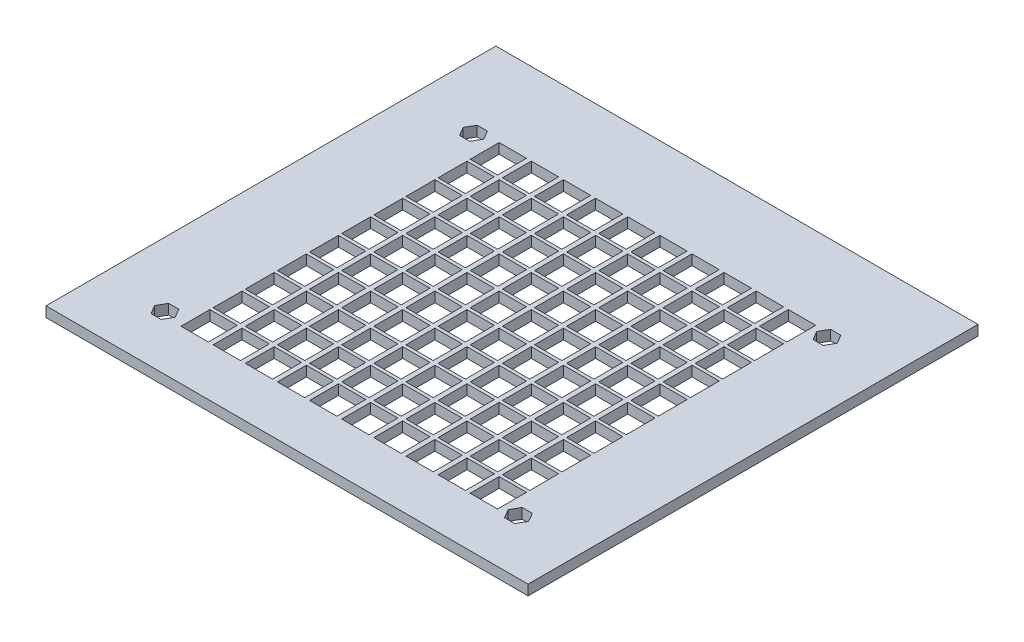
SolidWorks part; units mm, degrees
ref_plane "Front Plane" through (0, 0, 0) normal (0, 0, 1) x (1, 0, 0)
ref_plane "Top Plane" through (0, 0, 0) normal (0, 1, 0) x (1, 0, 0)
ref_plane "Right Plane" through (0, 0, 0) normal (1, 0, 0) x (0, 0, -1)
sketch "Sketch1" plane through (0, 0, 0) normal (0, 1, 0) x (1, 0, 0)
  line L0 (130, 101) -> (20, 101) construction
  line L2 (0, 0) -> (0, 106)
  line L4 (150, 0) -> (150, 106)
  line L6 (130, 101) -> (130, 5) construction
  line L8 (21.5877, 98.25) -> (23.1754, 101)
  line L9 (23.1754, 101) -> (21.5877, 103.75)
  line L10 (21.5877, 103.75) -> (18.4123, 103.75)
  line L11 (18.4123, 103.75) -> (16.8246, 101)
  line L12 (16.8246, 101) -> (18.4123, 98.25)
  line L13 (18.4123, 98.25) -> (21.5877, 98.25)
  line L14 (36.5, 12.5) -> (36.5, 3.5)
  line L15 (26.5, 12.5) -> (35, 12.5)
  line L16 (26.5, 12.5) -> (26.5, 3.5)
  line L17 (26.5, 3.5) -> (35, 3.5)
  line L18 (35, 12.5) -> (35, 3.5)
  line L19 (36.5, 12.5) -> (45, 12.5)
  line L20 (45, 12.5) -> (45, 3.5)
  line L21 (36.5, 3.5) -> (45, 3.5)
  line L22 (46.5, 12.5) -> (46.5, 3.5)
  line L23 (46.5, 12.5) -> (55, 12.5)
  line L24 (55, 12.5) -> (55, 3.5)
  line L25 (46.5, 3.5) -> (55, 3.5)
  line L26 (56.5, 12.5) -> (56.5, 3.5)
  line L27 (56.5, 12.5) -> (65, 12.5)
  line L28 (65, 12.5) -> (65, 3.5)
  line L29 (56.5, 3.5) -> (65, 3.5)
  line L30 (66.5, 12.5) -> (66.5, 3.5)
  line L31 (66.5, 12.5) -> (75, 12.5)
  line L32 (75, 12.5) -> (75, 3.5)
  line L33 (66.5, 3.5) -> (75, 3.5)
  line L34 (76.5, 12.5) -> (76.5, 3.5)
  line L35 (76.5, 12.5) -> (85, 12.5)
  line L36 (85, 12.5) -> (85, 3.5)
  line L37 (76.5, 3.5) -> (85, 3.5)
  line L38 (86.5, 12.5) -> (86.5, 3.5)
  line L39 (86.5, 12.5) -> (95, 12.5)
  line L40 (95, 12.5) -> (95, 3.5)
  line L41 (86.5, 3.5) -> (95, 3.5)
  line L42 (96.5, 12.5) -> (96.5, 3.5)
  line L43 (96.5, 12.5) -> (105, 12.5)
  line L44 (105, 12.5) -> (105, 3.5)
  line L45 (96.5, 3.5) -> (105, 3.5)
  line L46 (106.5, 12.5) -> (106.5, 3.5)
  line L47 (106.5, 12.5) -> (115, 12.5)
  line L48 (115, 12.5) -> (115, 3.5)
  line L49 (106.5, 3.5) -> (115, 3.5)
  line L50 (116.5, 12.5) -> (116.5, 3.5)
  line L51 (116.5, 12.5) -> (125, 12.5)
  line L52 (125, 12.5) -> (125, 3.5)
  line L53 (116.5, 3.5) -> (125, 3.5)
  line L54 (36.5, 22.5) -> (36.5, 13.5)
  line L55 (36.5, 22.5) -> (45, 22.5)
  line L56 (45, 22.5) -> (45, 13.5)
  line L57 (36.5, 13.5) -> (45, 13.5)
  line L58 (46.5, 22.5) -> (46.5, 13.5)
  line L59 (46.5, 22.5) -> (55, 22.5)
  line L60 (55, 22.5) -> (55, 13.5)
  line L61 (46.5, 13.5) -> (55, 13.5)
  line L62 (56.5, 22.5) -> (56.5, 13.5)
  line L63 (56.5, 22.5) -> (65, 22.5)
  line L64 (65, 22.5) -> (65, 13.5)
  line L65 (56.5, 13.5) -> (65, 13.5)
  line L66 (66.5, 22.5) -> (66.5, 13.5)
  line L67 (66.5, 22.5) -> (75, 22.5)
  line L68 (75, 22.5) -> (75, 13.5)
  line L69 (66.5, 13.5) -> (75, 13.5)
  line L70 (76.5, 22.5) -> (76.5, 13.5)
  line L71 (76.5, 22.5) -> (85, 22.5)
  line L72 (85, 22.5) -> (85, 13.5)
  line L73 (76.5, 13.5) -> (85, 13.5)
  line L74 (86.5, 22.5) -> (86.5, 13.5)
  line L75 (86.5, 22.5) -> (95, 22.5)
  line L76 (95, 22.5) -> (95, 13.5)
  line L77 (86.5, 13.5) -> (95, 13.5)
  line L78 (96.5, 22.5) -> (96.5, 13.5)
  line L79 (96.5, 22.5) -> (105, 22.5)
  line L80 (105, 22.5) -> (105, 13.5)
  line L81 (96.5, 13.5) -> (105, 13.5)
  line L82 (106.5, 22.5) -> (106.5, 13.5)
  line L83 (106.5, 22.5) -> (115, 22.5)
  line L84 (115, 22.5) -> (115, 13.5)
  line L85 (106.5, 13.5) -> (115, 13.5)
  line L86 (116.5, 22.5) -> (116.5, 13.5)
  line L87 (116.5, 22.5) -> (125, 22.5)
  line L88 (125, 22.5) -> (125, 13.5)
  line L89 (116.5, 13.5) -> (125, 13.5)
  line L90 (36.5, 32.5) -> (36.5, 23.5)
  line L91 (36.5, 32.5) -> (45, 32.5)
  line L92 (45, 32.5) -> (45, 23.5)
  line L93 (36.5, 23.5) -> (45, 23.5)
  line L94 (46.5, 32.5) -> (46.5, 23.5)
  line L95 (46.5, 32.5) -> (55, 32.5)
  line L96 (55, 32.5) -> (55, 23.5)
  line L97 (46.5, 23.5) -> (55, 23.5)
  line L98 (56.5, 32.5) -> (56.5, 23.5)
  line L99 (56.5, 32.5) -> (65, 32.5)
  line L100 (65, 32.5) -> (65, 23.5)
  line L101 (56.5, 23.5) -> (65, 23.5)
  line L102 (66.5, 32.5) -> (66.5, 23.5)
  line L103 (66.5, 32.5) -> (75, 32.5)
  line L104 (75, 32.5) -> (75, 23.5)
  line L105 (66.5, 23.5) -> (75, 23.5)
  line L106 (76.5, 32.5) -> (76.5, 23.5)
  line L107 (76.5, 32.5) -> (85, 32.5)
  line L108 (85, 32.5) -> (85, 23.5)
  line L109 (76.5, 23.5) -> (85, 23.5)
  line L110 (86.5, 32.5) -> (86.5, 23.5)
  line L111 (86.5, 32.5) -> (95, 32.5)
  line L112 (95, 32.5) -> (95, 23.5)
  line L113 (86.5, 23.5) -> (95, 23.5)
  line L114 (96.5, 32.5) -> (96.5, 23.5)
  line L115 (96.5, 32.5) -> (105, 32.5)
  line L116 (105, 32.5) -> (105, 23.5)
  line L117 (96.5, 23.5) -> (105, 23.5)
  line L118 (106.5, 32.5) -> (106.5, 23.5)
  line L119 (106.5, 32.5) -> (115, 32.5)
  line L120 (115, 32.5) -> (115, 23.5)
  line L121 (106.5, 23.5) -> (115, 23.5)
  line L122 (116.5, 32.5) -> (116.5, 23.5)
  line L123 (116.5, 32.5) -> (125, 32.5)
  line L124 (125, 32.5) -> (125, 23.5)
  line L125 (116.5, 23.5) -> (125, 23.5)
  line L126 (36.5, 42.5) -> (36.5, 33.5)
  line L127 (36.5, 42.5) -> (45, 42.5)
  line L128 (45, 42.5) -> (45, 33.5)
  line L129 (36.5, 33.5) -> (45, 33.5)
  line L130 (46.5, 42.5) -> (46.5, 33.5)
  line L131 (46.5, 42.5) -> (55, 42.5)
  line L132 (55, 42.5) -> (55, 33.5)
  line L133 (46.5, 33.5) -> (55, 33.5)
  line L134 (56.5, 42.5) -> (56.5, 33.5)
  line L135 (56.5, 42.5) -> (65, 42.5)
  line L136 (65, 42.5) -> (65, 33.5)
  line L137 (56.5, 33.5) -> (65, 33.5)
  line L138 (66.5, 42.5) -> (66.5, 33.5)
  line L139 (66.5, 42.5) -> (75, 42.5)
  line L140 (75, 42.5) -> (75, 33.5)
  line L141 (66.5, 33.5) -> (75, 33.5)
  line L142 (76.5, 42.5) -> (76.5, 33.5)
  line L143 (76.5, 42.5) -> (85, 42.5)
  line L144 (85, 42.5) -> (85, 33.5)
  line L145 (76.5, 33.5) -> (85, 33.5)
  line L146 (86.5, 42.5) -> (86.5, 33.5)
  line L147 (86.5, 42.5) -> (95, 42.5)
  line L148 (95, 42.5) -> (95, 33.5)
  line L149 (86.5, 33.5) -> (95, 33.5)
  line L150 (96.5, 42.5) -> (96.5, 33.5)
  line L151 (96.5, 42.5) -> (105, 42.5)
  line L152 (105, 42.5) -> (105, 33.5)
  line L153 (96.5, 33.5) -> (105, 33.5)
  line L154 (106.5, 42.5) -> (106.5, 33.5)
  line L155 (106.5, 42.5) -> (115, 42.5)
  line L156 (115, 42.5) -> (115, 33.5)
  line L157 (106.5, 33.5) -> (115, 33.5)
  line L158 (116.5, 42.5) -> (116.5, 33.5)
  line L159 (116.5, 42.5) -> (125, 42.5)
  line L160 (125, 42.5) -> (125, 33.5)
  line L161 (116.5, 33.5) -> (125, 33.5)
  line L162 (36.5, 52.5) -> (36.5, 43.5)
  line L163 (36.5, 52.5) -> (45, 52.5)
  line L164 (45, 52.5) -> (45, 43.5)
  line L165 (36.5, 43.5) -> (45, 43.5)
  line L166 (46.5, 52.5) -> (46.5, 43.5)
  line L167 (46.5, 52.5) -> (55, 52.5)
  line L168 (55, 52.5) -> (55, 43.5)
  line L169 (46.5, 43.5) -> (55, 43.5)
  line L170 (56.5, 52.5) -> (56.5, 43.5)
  line L171 (56.5, 52.5) -> (65, 52.5)
  line L172 (65, 52.5) -> (65, 43.5)
  line L173 (56.5, 43.5) -> (65, 43.5)
  line L174 (66.5, 52.5) -> (66.5, 43.5)
  line L175 (66.5, 52.5) -> (75, 52.5)
  line L176 (75, 52.5) -> (75, 43.5)
  line L177 (66.5, 43.5) -> (75, 43.5)
  line L178 (76.5, 52.5) -> (76.5, 43.5)
  line L179 (76.5, 52.5) -> (85, 52.5)
  line L180 (85, 52.5) -> (85, 43.5)
  line L181 (76.5, 43.5) -> (85, 43.5)
  line L182 (86.5, 52.5) -> (86.5, 43.5)
  line L183 (86.5, 52.5) -> (95, 52.5)
  line L184 (95, 52.5) -> (95, 43.5)
  line L185 (86.5, 43.5) -> (95, 43.5)
  line L186 (96.5, 52.5) -> (96.5, 43.5)
  line L187 (96.5, 52.5) -> (105, 52.5)
  line L188 (105, 52.5) -> (105, 43.5)
  line L189 (96.5, 43.5) -> (105, 43.5)
  line L190 (106.5, 52.5) -> (106.5, 43.5)
  line L191 (106.5, 52.5) -> (115, 52.5)
  line L192 (115, 52.5) -> (115, 43.5)
  line L193 (106.5, 43.5) -> (115, 43.5)
  line L194 (116.5, 52.5) -> (116.5, 43.5)
  line L195 (116.5, 52.5) -> (125, 52.5)
  line L196 (125, 52.5) -> (125, 43.5)
  line L197 (116.5, 43.5) -> (125, 43.5)
  line L198 (36.5, 62.5) -> (36.5, 53.5)
  line L199 (36.5, 62.5) -> (45, 62.5)
  line L200 (45, 62.5) -> (45, 53.5)
  line L201 (36.5, 53.5) -> (45, 53.5)
  line L202 (46.5, 62.5) -> (46.5, 53.5)
  line L203 (46.5, 62.5) -> (55, 62.5)
  line L204 (55, 62.5) -> (55, 53.5)
  line L205 (46.5, 53.5) -> (55, 53.5)
  line L206 (56.5, 62.5) -> (56.5, 53.5)
  line L207 (56.5, 62.5) -> (65, 62.5)
  line L208 (65, 62.5) -> (65, 53.5)
  line L209 (56.5, 53.5) -> (65, 53.5)
  line L210 (66.5, 62.5) -> (66.5, 53.5)
  line L211 (66.5, 62.5) -> (75, 62.5)
  line L212 (75, 62.5) -> (75, 53.5)
  line L213 (66.5, 53.5) -> (75, 53.5)
  line L214 (76.5, 62.5) -> (76.5, 53.5)
  line L215 (76.5, 62.5) -> (85, 62.5)
  line L216 (85, 62.5) -> (85, 53.5)
  line L217 (76.5, 53.5) -> (85, 53.5)
  line L218 (86.5, 62.5) -> (86.5, 53.5)
  line L219 (86.5, 62.5) -> (95, 62.5)
  line L220 (95, 62.5) -> (95, 53.5)
  line L221 (86.5, 53.5) -> (95, 53.5)
  line L222 (96.5, 62.5) -> (96.5, 53.5)
  line L223 (96.5, 62.5) -> (105, 62.5)
  line L224 (105, 62.5) -> (105, 53.5)
  line L225 (96.5, 53.5) -> (105, 53.5)
  line L226 (106.5, 62.5) -> (106.5, 53.5)
  line L227 (106.5, 62.5) -> (115, 62.5)
  line L228 (115, 62.5) -> (115, 53.5)
  line L229 (106.5, 53.5) -> (115, 53.5)
  line L230 (116.5, 62.5) -> (116.5, 53.5)
  line L231 (116.5, 62.5) -> (125, 62.5)
  line L232 (125, 62.5) -> (125, 53.5)
  line L233 (116.5, 53.5) -> (125, 53.5)
  line L234 (36.5, 72.5) -> (36.5, 63.5)
  line L235 (36.5, 72.5) -> (45, 72.5)
  line L236 (45, 72.5) -> (45, 63.5)
  line L237 (36.5, 63.5) -> (45, 63.5)
  line L238 (46.5, 72.5) -> (46.5, 63.5)
  line L239 (46.5, 72.5) -> (55, 72.5)
  line L240 (55, 72.5) -> (55, 63.5)
  line L241 (46.5, 63.5) -> (55, 63.5)
  line L242 (56.5, 72.5) -> (56.5, 63.5)
  line L243 (56.5, 72.5) -> (65, 72.5)
  line L244 (65, 72.5) -> (65, 63.5)
  line L245 (56.5, 63.5) -> (65, 63.5)
  line L246 (66.5, 72.5) -> (66.5, 63.5)
  line L247 (66.5, 72.5) -> (75, 72.5)
  line L248 (75, 72.5) -> (75, 63.5)
  line L249 (66.5, 63.5) -> (75, 63.5)
  line L250 (76.5, 72.5) -> (76.5, 63.5)
  line L251 (76.5, 72.5) -> (85, 72.5)
  line L252 (85, 72.5) -> (85, 63.5)
  line L253 (76.5, 63.5) -> (85, 63.5)
  line L254 (86.5, 72.5) -> (86.5, 63.5)
  line L255 (86.5, 72.5) -> (95, 72.5)
  line L256 (95, 72.5) -> (95, 63.5)
  line L257 (86.5, 63.5) -> (95, 63.5)
  line L258 (96.5, 72.5) -> (96.5, 63.5)
  line L259 (96.5, 72.5) -> (105, 72.5)
  line L260 (105, 72.5) -> (105, 63.5)
  line L261 (96.5, 63.5) -> (105, 63.5)
  line L262 (106.5, 72.5) -> (106.5, 63.5)
  line L263 (106.5, 72.5) -> (115, 72.5)
  line L264 (115, 72.5) -> (115, 63.5)
  line L265 (106.5, 63.5) -> (115, 63.5)
  line L266 (116.5, 72.5) -> (116.5, 63.5)
  line L267 (116.5, 72.5) -> (125, 72.5)
  line L268 (125, 72.5) -> (125, 63.5)
  line L269 (116.5, 63.5) -> (125, 63.5)
  line L270 (36.5, 82.5) -> (36.5, 73.5)
  line L271 (36.5, 82.5) -> (45, 82.5)
  line L272 (45, 82.5) -> (45, 73.5)
  line L273 (36.5, 73.5) -> (45, 73.5)
  line L274 (46.5, 82.5) -> (46.5, 73.5)
  line L275 (46.5, 82.5) -> (55, 82.5)
  line L276 (55, 82.5) -> (55, 73.5)
  line L277 (46.5, 73.5) -> (55, 73.5)
  line L278 (56.5, 82.5) -> (56.5, 73.5)
  line L279 (56.5, 82.5) -> (65, 82.5)
  line L280 (65, 82.5) -> (65, 73.5)
  line L281 (56.5, 73.5) -> (65, 73.5)
  line L282 (66.5, 82.5) -> (66.5, 73.5)
  line L283 (66.5, 82.5) -> (75, 82.5)
  line L284 (75, 82.5) -> (75, 73.5)
  line L285 (66.5, 73.5) -> (75, 73.5)
  line L286 (76.5, 82.5) -> (76.5, 73.5)
  line L287 (76.5, 82.5) -> (85, 82.5)
  line L288 (85, 82.5) -> (85, 73.5)
  line L289 (76.5, 73.5) -> (85, 73.5)
  line L290 (86.5, 82.5) -> (86.5, 73.5)
  line L291 (86.5, 82.5) -> (95, 82.5)
  line L292 (95, 82.5) -> (95, 73.5)
  line L293 (86.5, 73.5) -> (95, 73.5)
  line L294 (96.5, 82.5) -> (96.5, 73.5)
  line L295 (96.5, 82.5) -> (105, 82.5)
  line L296 (105, 82.5) -> (105, 73.5)
  line L297 (96.5, 73.5) -> (105, 73.5)
  line L298 (106.5, 82.5) -> (106.5, 73.5)
  line L299 (106.5, 82.5) -> (115, 82.5)
  line L300 (115, 82.5) -> (115, 73.5)
  line L301 (106.5, 73.5) -> (115, 73.5)
  line L302 (116.5, 82.5) -> (116.5, 73.5)
  line L303 (116.5, 82.5) -> (125, 82.5)
  line L304 (125, 82.5) -> (125, 73.5)
  line L305 (116.5, 73.5) -> (125, 73.5)
  line L306 (36.5, 92.5) -> (36.5, 83.5)
  line L307 (36.5, 92.5) -> (45, 92.5)
  line L308 (45, 92.5) -> (45, 83.5)
  line L309 (36.5, 83.5) -> (45, 83.5)
  line L310 (46.5, 92.5) -> (46.5, 83.5)
  line L311 (46.5, 92.5) -> (55, 92.5)
  line L312 (55, 92.5) -> (55, 83.5)
  line L313 (46.5, 83.5) -> (55, 83.5)
  line L314 (56.5, 92.5) -> (56.5, 83.5)
  line L315 (56.5, 92.5) -> (65, 92.5)
  line L316 (65, 92.5) -> (65, 83.5)
  line L317 (56.5, 83.5) -> (65, 83.5)
  line L318 (66.5, 92.5) -> (66.5, 83.5)
  line L319 (66.5, 92.5) -> (75, 92.5)
  line L320 (75, 92.5) -> (75, 83.5)
  line L321 (66.5, 83.5) -> (75, 83.5)
  line L322 (76.5, 92.5) -> (76.5, 83.5)
  line L323 (76.5, 92.5) -> (85, 92.5)
  line L324 (85, 92.5) -> (85, 83.5)
  line L325 (76.5, 83.5) -> (85, 83.5)
  line L326 (86.5, 92.5) -> (86.5, 83.5)
  line L327 (86.5, 92.5) -> (95, 92.5)
  line L328 (95, 92.5) -> (95, 83.5)
  line L329 (86.5, 83.5) -> (95, 83.5)
  line L330 (96.5, 92.5) -> (96.5, 83.5)
  line L331 (96.5, 92.5) -> (105, 92.5)
  line L332 (105, 92.5) -> (105, 83.5)
  line L333 (96.5, 83.5) -> (105, 83.5)
  line L334 (106.5, 92.5) -> (106.5, 83.5)
  line L335 (106.5, 92.5) -> (115, 92.5)
  line L336 (115, 92.5) -> (115, 83.5)
  line L337 (106.5, 83.5) -> (115, 83.5)
  line L338 (116.5, 92.5) -> (116.5, 83.5)
  line L339 (116.5, 92.5) -> (125, 92.5)
  line L340 (125, 92.5) -> (125, 83.5)
  line L341 (116.5, 83.5) -> (125, 83.5)
  line L342 (36.5, 102.5) -> (36.5, 93.5)
  line L343 (36.5, 102.5) -> (45, 102.5)
  line L344 (45, 102.5) -> (45, 93.5)
  line L345 (36.5, 93.5) -> (45, 93.5)
  line L346 (46.5, 102.5) -> (46.5, 93.5)
  line L347 (46.5, 102.5) -> (55, 102.5)
  line L348 (55, 102.5) -> (55, 93.5)
  line L349 (46.5, 93.5) -> (55, 93.5)
  line L350 (56.5, 102.5) -> (56.5, 93.5)
  line L351 (56.5, 102.5) -> (65, 102.5)
  line L352 (65, 102.5) -> (65, 93.5)
  line L353 (56.5, 93.5) -> (65, 93.5)
  line L354 (66.5, 102.5) -> (66.5, 93.5)
  line L355 (66.5, 102.5) -> (75, 102.5)
  line L356 (75, 102.5) -> (75, 93.5)
  line L357 (66.5, 93.5) -> (75, 93.5)
  line L358 (76.5, 102.5) -> (76.5, 93.5)
  line L359 (76.5, 102.5) -> (85, 102.5)
  line L360 (85, 102.5) -> (85, 93.5)
  line L361 (76.5, 93.5) -> (85, 93.5)
  line L362 (86.5, 102.5) -> (86.5, 93.5)
  line L363 (86.5, 102.5) -> (95, 102.5)
  line L364 (95, 102.5) -> (95, 93.5)
  line L365 (86.5, 93.5) -> (95, 93.5)
  line L366 (96.5, 102.5) -> (96.5, 93.5)
  line L367 (96.5, 102.5) -> (105, 102.5)
  line L368 (105, 102.5) -> (105, 93.5)
  line L369 (96.5, 93.5) -> (105, 93.5)
  line L370 (106.5, 102.5) -> (106.5, 93.5)
  line L371 (106.5, 102.5) -> (115, 102.5)
  line L372 (115, 102.5) -> (115, 93.5)
  line L373 (106.5, 93.5) -> (115, 93.5)
  line L374 (116.5, 102.5) -> (116.5, 93.5)
  line L375 (116.5, 102.5) -> (125, 102.5)
  line L376 (125, 102.5) -> (125, 93.5)
  line L377 (116.5, 93.5) -> (125, 93.5)
  line L378 (26.5, 22.5) -> (26.5, 13.5)
  line L379 (26.5, 22.5) -> (35, 22.5)
  line L380 (35, 22.5) -> (35, 13.5)
  line L381 (26.5, 13.5) -> (35, 13.5)
  line L382 (26.5, 32.5) -> (26.5, 23.5)
  line L383 (26.5, 32.5) -> (35, 32.5)
  line L384 (35, 32.5) -> (35, 23.5)
  line L385 (26.5, 23.5) -> (35, 23.5)
  line L386 (26.5, 42.5) -> (26.5, 33.5)
  line L387 (26.5, 42.5) -> (35, 42.5)
  line L388 (35, 42.5) -> (35, 33.5)
  line L389 (26.5, 33.5) -> (35, 33.5)
  line L390 (26.5, 52.5) -> (26.5, 43.5)
  line L391 (26.5, 52.5) -> (35, 52.5)
  line L392 (35, 52.5) -> (35, 43.5)
  line L393 (26.5, 43.5) -> (35, 43.5)
  line L394 (26.5, 62.5) -> (26.5, 53.5)
  line L395 (26.5, 62.5) -> (35, 62.5)
  line L396 (35, 62.5) -> (35, 53.5)
  line L397 (26.5, 53.5) -> (35, 53.5)
  line L398 (26.5, 72.5) -> (26.5, 63.5)
  line L399 (26.5, 72.5) -> (35, 72.5)
  line L400 (35, 72.5) -> (35, 63.5)
  line L401 (26.5, 63.5) -> (35, 63.5)
  line L402 (26.5, 82.5) -> (26.5, 73.5)
  line L403 (26.5, 82.5) -> (35, 82.5)
  line L404 (35, 82.5) -> (35, 73.5)
  line L405 (26.5, 73.5) -> (35, 73.5)
  line L406 (26.5, 92.5) -> (26.5, 83.5)
  line L407 (26.5, 92.5) -> (35, 92.5)
  line L408 (35, 92.5) -> (35, 83.5)
  line L409 (26.5, 83.5) -> (35, 83.5)
  line L410 (26.5, 102.5) -> (26.5, 93.5)
  line L411 (26.5, 102.5) -> (35, 102.5)
  line L412 (35, 102.5) -> (35, 93.5)
  line L413 (26.5, 93.5) -> (35, 93.5)
  line L414 (150, 0) -> (150, -12)
  line L415 (128.4123, 103.75) -> (126.8246, 101)
  line L416 (126.8246, 101) -> (128.4123, 98.25)
  line L417 (128.4123, 98.25) -> (131.5877, 98.25)
  line L418 (131.5877, 98.25) -> (133.1754, 101)
  line L419 (133.1754, 101) -> (131.5877, 103.75)
  line L420 (131.5877, 103.75) -> (128.4123, 103.75)
  line L421 (128.4123, 7.75) -> (126.8246, 5)
  line L422 (126.8246, 5) -> (128.4123, 2.25)
  line L423 (128.4123, 2.25) -> (131.5877, 2.25)
  line L424 (131.5877, 2.25) -> (133.1754, 5)
  line L425 (133.1754, 5) -> (131.5877, 7.75)
  line L426 (131.5877, 7.75) -> (128.4123, 7.75)
  line L427 (16.8246, 5) -> (18.4123, 2.25)
  line L428 (18.4123, 2.25) -> (21.5877, 2.25)
  line L429 (21.5877, 2.25) -> (23.1754, 5)
  line L430 (23.1754, 5) -> (21.5877, 7.75)
  line L431 (21.5877, 7.75) -> (18.4123, 7.75)
  line L432 (18.4123, 7.75) -> (16.8246, 5)
  line L433 (150, -12) -> (0, -12)
  line L434 (0, -12) -> (0, 0)
  line L435 (0, 106) -> (0, 128)
  line L436 (0, 128) -> (150, 128)
  line L437 (150, 128) -> (150, 106)
  circle A28 centre (20, 5) radius 1.7
  circle A29 centre (20, 101) radius 1.7
  circle A30 centre (130, 101) radius 1.7
  circle A31 centre (130, 5) radius 1.7
  circle A129 centre (20, 101) radius 2.75 construction
  circle A130 centre (130, 101) radius 2.75 construction
  circle A131 centre (130, 5) radius 2.75 construction
  circle A132 centre (20, 5) radius 2.75 construction
  point P7 (130, 53)
  point P9 (75, 101)
  point P10 (0, 0)
  point P20 (150, 53)
  dimension "D3" = 9
  dimension "D7" = 10
  dimension "D11" = 1.5
  dimension "D9" = 10
extrude "Boss-Extrude1" add sketch "Sketch1" along normal blind 3.175 contours L4 L2 region at (2.0518, 0, -53)
equation "\"o\"= 10mm"
equation "\"P\"= 10"
